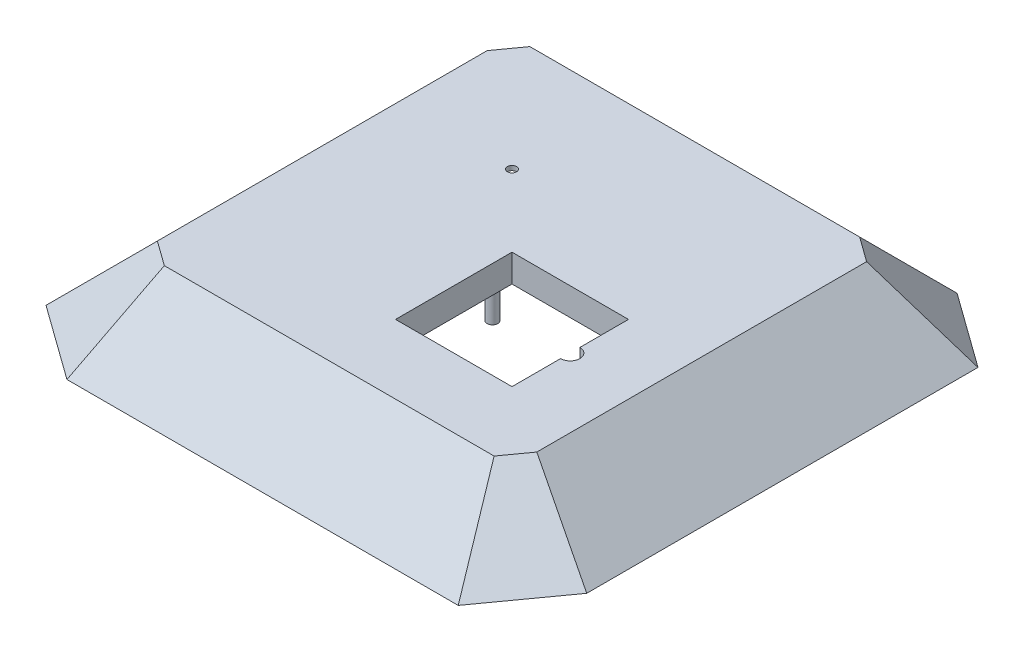
SolidWorks part; units mm, degrees
ref_plane "Front Plane" through (0, 0, 0) normal (0, 0, 1) x (1, 0, 0)
ref_plane "Top Plane" through (0, 0, 0) normal (0, 1, 0) x (1, 0, 0)
ref_plane "Right Plane" through (0, 0, 0) normal (1, 0, 0) x (0, 0, -1)
sketch "Sketch1" plane through (0, 0, 0) normal (0, 1, 0) x (1, 0, 0)
  line L0 (-47.3454, -21.7516) -> (37.6546, -21.7516)
  line L1 (37.6546, -21.7516) -> (49.3368, -5.5181)
  line L2 (49.3368, -5.5181) -> (49.3368, 79.4819)
  line L3 (49.3368, 79.4819) -> (33.1033, 91.1641)
  line L4 (33.1033, 91.1641) -> (-51.8967, 91.1641)
  line L5 (-51.8967, 91.1641) -> (-63.5789, 74.9306)
  line L6 (-63.5789, 74.9306) -> (-63.5789, -10.0694)
  line L7 (-63.5789, -10.0694) -> (-47.3454, -21.7516)
  dimension "D2" = 85
  dimension "D3" = 85
  dimension "D4" = 144.26
  dimension "D5" = 144.26
  dimension "D6" = 85
  dimension "D7" = 144.26
  dimension "D8" = 20
  dimension "D9" = 85
  dimension "D10" = 20
  dimension "D11" = 20
extrude "Boss-Extrude2" add sketch "Sketch1" along normal blind 16
sketch "Sketch4" plane through (0, 0, 0) normal (0, -1, 0) x (1, 0, 0)
  line L16 (-42.1868, 5.7516) -> (-47.5789, 1.8712)
  line L17 (-47.5789, 1.8712) -> (-47.5789, -69.772)
  line L18 (-47.5789, -69.772) -> (-43.6985, -75.1641)
  line L19 (-43.6985, -75.1641) -> (27.9447, -75.1641)
  line L20 (27.9447, -75.1641) -> (33.3368, -71.2838)
  line L21 (33.3368, -71.2838) -> (33.3368, 0.3594)
  line L22 (33.3368, 0.3594) -> (29.4564, 5.7516)
  line L23 (29.4564, 5.7516) -> (-42.1868, 5.7516)
  line L24 (-42.1868, 5.7516) -> (-47.5789, 1.8712)
  line L25 (-47.5789, 1.8712) -> (-47.5789, -69.772)
  line L26 (-47.5789, -69.772) -> (-43.6985, -75.1641)
  line L27 (-43.6985, -75.1641) -> (27.9447, -75.1641)
  line L28 (27.9447, -75.1641) -> (33.3368, -71.2838)
  line L29 (33.3368, -71.2838) -> (33.3368, 0.3594)
  line L30 (33.3368, 0.3594) -> (29.4564, 5.7516)
  line L31 (29.4564, 5.7516) -> (-42.1868, 5.7516)
  dimension "D1" = 16
chamfer "Chamfer1" distance 16 angle 45 8 edges at (-63.5789, 16, -32.4306) (-57.7378, 16, -83.0473) (-9.3967, 16, -91.1641) (41.22, 16, -85.323) (49.3368, 16, -36.9819) (43.4957, 16, 13.6348) (-4.8454, 16, 21.7516) (-55.4621, 16, 15.9105)
extrude "Cut-Extrude3" cut sketch "Sketch4" against normal blind 10
sketch "Sketch6" plane through (0, 16, 0) normal (0, 1, 0) x (1, 0, 0)
  line L0 (33.3368, -0.3594) -> (33.3368, 71.2838) construction
  line L1 (-6.9632, 34.5484) -> (18.3368, 34.5484)
  line L2 (-6.9632, 34.5484) -> (-6.9632, 9.2484)
  line L3 (-6.9632, 9.2484) -> (18.3368, 9.2484)
  line L4 (18.3368, 34.5484) -> (18.3368, 9.2484)
  line L5 (-42.1868, -5.7516) -> (29.4564, -5.7516) construction
  dimension "D1" = 25.3
  dimension "D2" = 25.3
  dimension "D3" = 15
  dimension "D4" = 15
extrude "Cut-Extrude4" cut sketch "Sketch6" against normal up to next
sketch "Sketch7" plane through (0, 10, 0) normal (0, -1, 0) x (1, 0, 0)
  line L0 (18.3368, -9.2484) -> (18.3368, -34.5484) construction
  circle A0 centre (18.3368, -21.8984) radius 2.0981
extrude "Cut-Extrude5" cut sketch "Sketch7" against normal up to next
sketch "Sketch8" plane through (0, 10, 0) normal (0, -1, 0) x (1, 0, 0)
  line L0 (-11.7632, -21.9984) -> (30.1662, -21.9984) construction
  line L1 (-11.7632, -8.8984) -> (24.2368, -8.8984)
  line L2 (-11.7632, -8.8984) -> (-11.7632, -35.0984)
  line L3 (-11.7632, -35.0984) -> (24.2368, -35.0984)
  line L4 (24.2368, -8.8984) -> (24.2368, -35.0984)
  line L5 (6.2368, -8.8984) -> (6.2368, -38.2867) construction
  line L6 (33.3368, -71.2838) -> (33.3368, 0.3594) construction
  line L7 (29.4564, 5.7516) -> (-42.1868, 5.7516) construction
  circle A0 centre (-9.2132, -11.4484) radius 1.15
  circle A1 centre (21.6868, -11.4484) radius 1.15
  circle A2 centre (21.6868, -32.5484) radius 1.15
  circle A3 centre (-9.2132, -32.5484) radius 1.15
  point P16 (0, 0)
  dimension "D3" = 2.3
  dimension "D4" = 2.55
  dimension "D5" = 2.55
  dimension "D6" = 9.1
  dimension "D1" = 36
  dimension "D2" = 26.2
  dimension "D7" = 14.65
extrude "Boss-Extrude3" add sketch "Sketch8" along normal blind 7 contours A0 | A1 | A2 | A3 region at (-9.2132, 10, -11.4484) region at (21.6868, 10, -11.4484) region at (21.6868, 10, -32.5484)
sketch "Sketch9" plane through (0, 10, 0) normal (0, -1, 0) x (1, 0, 0)
  line L2 (-47.5789, 1.8712) -> (-47.5789, -69.772) construction
  line L3 (-43.6985, -75.1641) -> (27.9447, -75.1641) construction
  circle A0 centre (-22.5789, -50.1641) radius 15.65
  dimension "D1" = 25
  dimension "D2" = 25
  dimension "D3" = 31.3
extrude "Cut-Extrude6" cut sketch "Sketch9" against normal blind 5
sketch "Sketch10" plane through (0, 15, 0) normal (0, -1, 0) x (1, 0, 0)
  circle A0 centre (-22.5789, -50.1641) radius 1
  dimension "D1" = 2
extrude "Cut-Extrude7" cut sketch "Sketch10" against normal up to next
